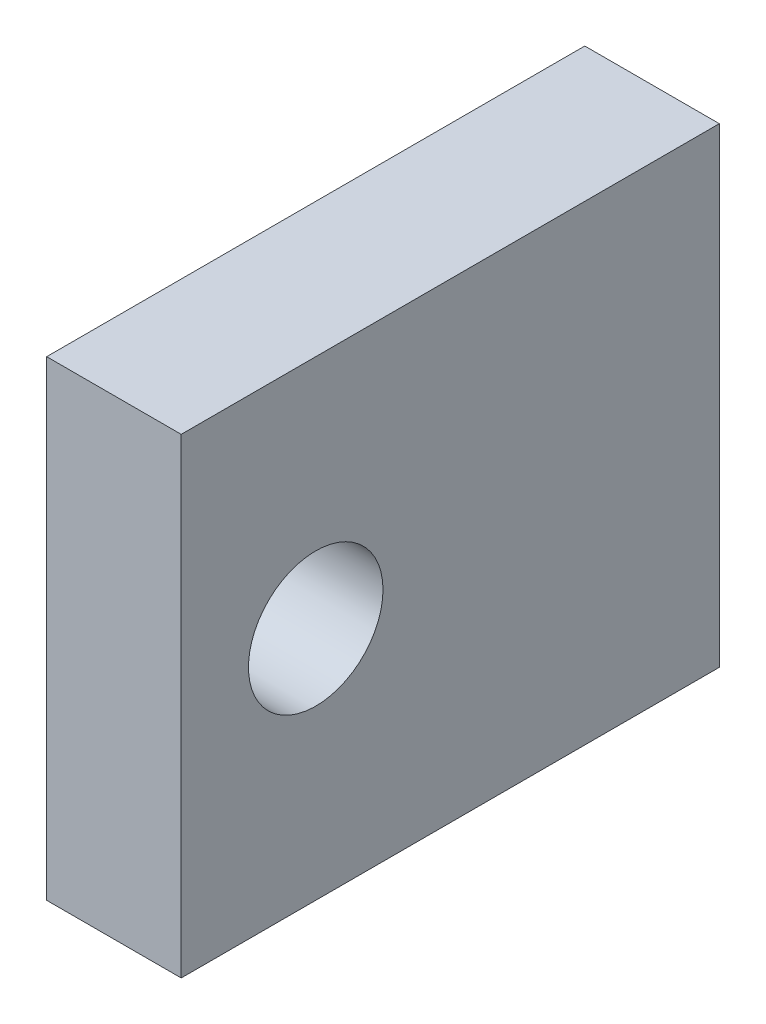
SolidWorks part; units mm, degrees
ref_plane "Front Plane" through (0, 0, 0) normal (0, 0, 1) x (1, 0, 0)
ref_plane "Top Plane" through (0, 0, 0) normal (0, 1, 0) x (1, 0, 0)
ref_plane "Right Plane" through (0, 0, 0) normal (1, 0, 0) x (0, 0, -1)
sketch "Sketch1" plane through (0, 0, 0) normal (1, 0, 0) x (0, 0, -1)
  line L1 (-25.4, -22.225) -> (25.4, -22.225)
  line L2 (-25.4, -22.225) -> (-25.4, 22.225)
  line L3 (-25.4, 22.225) -> (25.4, 22.225)
  line L4 (25.4, -22.225) -> (25.4, 22.225)
  line L5 (-25.4, -22.225) -> (25.4, 22.225) construction
  line L6 (-25.4, 22.225) -> (25.4, -22.225) construction
  circle A0 centre (-12.7, 0) radius 6.35
  point P0 (0, 0)
  dimension "D2" = 12.7
  dimension "D3" = 38.1
  dimension "D1" = 50.8
  dimension "D4" = 44.45
extrude "Boss-Extrude1" add sketch "Sketch1" along normal blind 12.7
